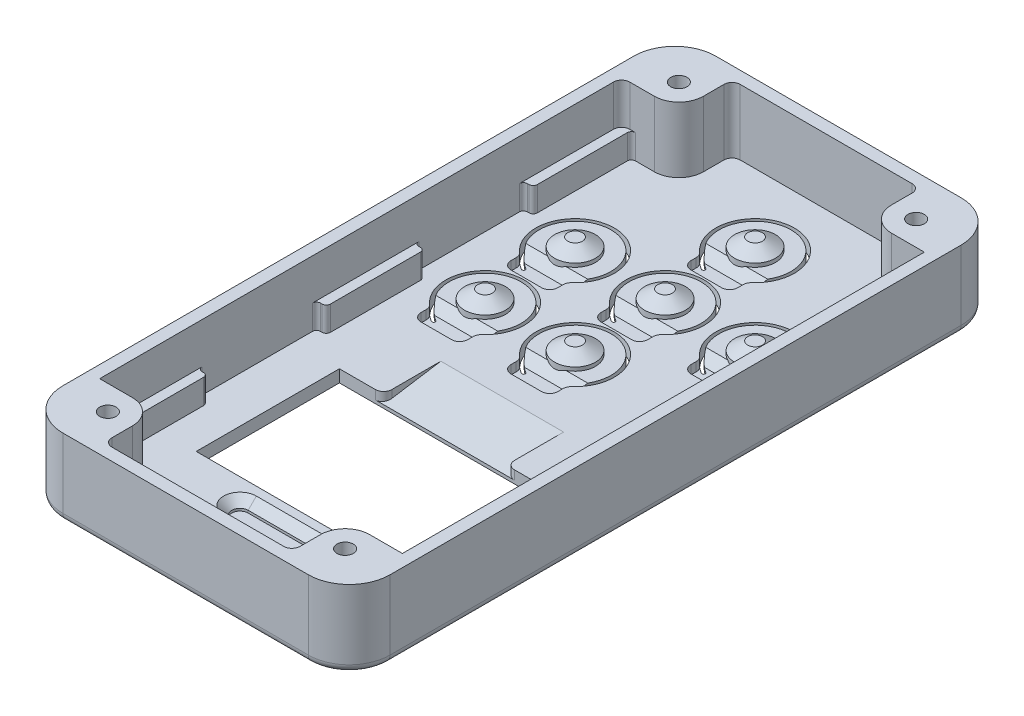
SolidWorks part; units mm, degrees
ref_plane "Front Plane" through (0, 0, 0) normal (0, 0, 1) x (1, 0, 0)
ref_plane "Top Plane" through (0, 0, 0) normal (0, 1, 0) x (1, 0, 0)
ref_plane "Right Plane" through (0, 0, 0) normal (1, 0, 0) x (0, 0, -1)
sketch "Base Sketch" plane through (0, 0, 0) normal (0, 1, 0) x (1, 0, 0)
  line L0 (0, 0) -> (40, 0)
  line L1 (40, 0) -> (40, 79.79)
  line L2 (40, 79.79) -> (0, 79.79)
  line L3 (0, 79.79) -> (0, 0)
extrude "Base" add sketch "Base Sketch" along normal blind 9.5
fillet "Corner Rounds R5" radius 5 4 edges at (0, 4.75, -79.79) (40, 4.75, -79.79) (40, 4.75, 0) (0, 4.75, 0)
shell "Shell 1.5" thickness 1.5 removed face at (20, 9.5, -39.895)
sketch "Boss Sketch" plane through (0, 0, 0) normal (0, 1, 0) x (1, 0, 0)
  line L0 (1.5, 1.5) -> (8.5, 1.5)
  line L1 (8.5, 1.5) -> (8.5, 5)
  line L2 (5.5, 8) -> (1.5, 8)
  line L3 (1.5, 8) -> (1.5, 1.5)
  line L4 (38.5, 1.5) -> (31.5, 1.5)
  line L5 (31.5, 1.5) -> (31.5, 5)
  line L6 (34.5, 8) -> (38.5, 8)
  line L7 (38.5, 8) -> (38.5, 1.5)
  line L16 (1.5, 78.29) -> (8.5, 78.29)
  line L17 (8.5, 78.29) -> (8.5, 74.79)
  line L18 (5.5, 71.79) -> (1.5, 71.79)
  line L19 (1.5, 71.79) -> (1.5, 78.29)
  line L20 (38.5, 78.29) -> (31.5, 78.29)
  line L21 (31.5, 78.29) -> (31.5, 74.79)
  line L22 (34.5, 71.79) -> (38.5, 71.79)
  line L23 (38.5, 71.79) -> (38.5, 78.29)
  arc A0 (8.5, 5) -> (5.5, 8) centre (5.4999, 4.9999) ccw
  circle A1 centre (5.5, 5) radius 1
  arc A2 (31.5, 5) -> (34.5, 8) centre (34.5001, 4.9999) cw
  circle A3 centre (34.5, 5) radius 1
  circle A5 centre (5.5, 74.79) radius 1
  circle A7 centre (34.5, 74.79) radius 1
  arc A8 (8.5, 74.79) -> (5.5, 71.79) centre (5.4999, 74.7901) cw
  arc A9 (31.5, 74.79) -> (34.5, 71.79) centre (34.5001, 74.7901) ccw
extrude "Corner Bosses + M2 Pilot Holes" add sketch "Boss Sketch" along normal blind 9.5
sketch "Ledge Sketch" plane through (0, 0, 0) normal (0, 1, 0) x (1, 0, 0)
  line L0 (1.5, 8) -> (2.7, 8)
  line L1 (2.7, 8) -> (2.7, 20)
  line L2 (2.7, 20) -> (1.5, 20)
  line L3 (1.5, 20) -> (1.5, 8)
  line L4 (37.3, 8) -> (38.5, 8)
  line L5 (38.5, 8) -> (38.5, 20)
  line L6 (38.5, 20) -> (37.3, 20)
  line L7 (37.3, 20) -> (37.3, 8)
  line L8 (1.5, 34.5) -> (2.7, 34.5)
  line L9 (2.7, 34.5) -> (2.7, 46.5)
  line L10 (2.7, 46.5) -> (1.5, 46.5)
  line L11 (1.5, 46.5) -> (1.5, 34.5)
  line L12 (37.3, 34.5) -> (38.5, 34.5)
  line L13 (38.5, 34.5) -> (38.5, 46.5)
  line L14 (38.5, 46.5) -> (37.3, 46.5)
  line L15 (37.3, 46.5) -> (37.3, 34.5)
  line L16 (1.5, 59.79) -> (2.7, 59.79)
  line L17 (2.7, 59.79) -> (2.7, 71.79)
  line L18 (2.7, 71.79) -> (1.5, 71.79)
  line L19 (1.5, 71.79) -> (1.5, 59.79)
  line L20 (37.3, 59.79) -> (38.5, 59.79)
  line L21 (38.5, 59.79) -> (38.5, 71.79)
  line L22 (38.5, 71.79) -> (37.3, 71.79)
  line L23 (37.3, 71.79) -> (37.3, 59.79)
extrude "Side Ledges" add sketch "Ledge Sketch" along normal blind 4.5
fillet "Outer Face Round R1" radius 1 8 edges at (1.4645, 0, -1.4645) (20, 0, 0) (38.5355, 0, -1.4645) (40, 0, -39.895) (38.5355, 0, -78.3255) (20, 0, -79.79) (1.4645, 0, -78.3255) (0, 0, -39.895)
sketch "Window Sketch" plane through (0, 0, 0) normal (0, 1, 0) x (1, 0, 0)
  line L0 (7.1, 14.5) -> (32.9, 14.5)
  line L1 (32.9, 14.5) -> (32.9, 31.7)
  line L2 (32.9, 31.7) -> (7.1, 31.7)
  line L3 (7.1, 31.7) -> (7.1, 14.5)
extrude "Display Window" cut sketch "Window Sketch" along normal through all
ref_plane "Mid Plane X20" through (20, 0, 0) normal (1, 0, 0) x (0, 0, -1)
sketch "Ramp Sketch" plane through (20, 0, 0) normal (1, 0, 0) x (0, 0, -1)
  line L0 (31, 0.4) -> (31.7, 0.4)
  line L1 (31.7, 0.4) -> (38.7, 1.5)
  line L2 (38.7, 1.5) -> (38.7, 2.5)
  line L3 (38.7, 2.5) -> (31, 2.5)
  line L4 (31, 2.5) -> (31, 0.4)
extrude "Cable Ramp" cut sketch "Ramp Sketch" against normal blind 7.5 and the other way blind 7.5
ref_plane "Plate Inner Face" through (0, 1.5, 0) normal (0, 1, 0) x (1, 0, 0)
sketch "LED Window Sketch" plane through (0, 1.5, 0) normal (0, 1, 0) x (1, 0, 0)
  circle A0 centre (20, 7.28) radius 1.7
  point P2 (0, 0)
  point P3 (0, 0)
  dimension "D1" = 3.4
extrude "LED Window" cut sketch "LED Window Sketch" against normal blind 1.3
sketch "Plunger Stems Sketch" plane through (0, 1.5, 0) normal (0, 1, 0) x (1, 0, 0)
  circle A0 centre (9, 47.6) radius 2.5
  circle A1 centre (20, 47.6) radius 2.5
  circle A2 centre (9, 58.6) radius 2.5
  circle A3 centre (20, 58.6) radius 2.5
  circle A4 centre (31, 58.6) radius 2.5
  circle A5 centre (20, 69.6) radius 2.5
extrude "Plunger Stems 5.0" add sketch "Plunger Stems Sketch" along normal blind 0.45
ref_plane "Plunger Cone Base" through (0, 1.95, 0) normal (0, 1, 0) x (1, 0, 0)
sketch "Plunger Cone Sketch" plane through (0, 1.95, 0) normal (0, 1, 0) x (1, 0, 0)
  circle A0 centre (9, 47.6) radius 2.5
  circle A1 centre (20, 47.6) radius 2.5
  circle A2 centre (9, 58.6) radius 2.5
  circle A3 centre (20, 58.6) radius 2.5
  circle A4 centre (31, 58.6) radius 2.5
  circle A5 centre (20, 69.6) radius 2.5
extrude "Plunger Cones to 1.8" add sketch "Plunger Cone Sketch" along normal blind 1 draft 57.995
fillet "Boss Junction Fillets R1" radius 1 8 edges at (1.5, 7, -71.79) (37.3, 3, -71.79) (37.3, 3, -8) (2.7, 3, -8) (31.5, 5.5, -78.29) (8.5, 5.5, -78.29) (31.5, 5.5, -1.5) (8.5, 5.5, -1.5)
sketch "C-Slot Sketch" plane through (0, 0, 0) normal (0, 1, 0) x (1, 0, 0)
  arc A0 (10.4434, 43.0222) -> (7.5566, 43.0222) centre (9, 47.6) ccw
  arc A1 (7.5566, 43.0222) -> (7.6769, 43.4036) centre (7.6168, 43.2129) ccw
  arc A2 (7.6769, 43.4036) -> (10.3231, 43.4036) centre (9, 47.6) cw
  arc A3 (10.3231, 43.4036) -> (10.4434, 43.0222) centre (10.3832, 43.2129) ccw
  arc A4 (21.4434, 43.0222) -> (18.5566, 43.0222) centre (20, 47.6) ccw
  arc A5 (18.5566, 43.0222) -> (18.6769, 43.4036) centre (18.6168, 43.2129) ccw
  arc A6 (18.6769, 43.4036) -> (21.3231, 43.4036) centre (20, 47.6) cw
  arc A7 (21.3231, 43.4036) -> (21.4434, 43.0222) centre (21.3832, 43.2129) ccw
  arc A8 (10.4434, 54.0222) -> (7.5566, 54.0222) centre (9, 58.6) ccw
  arc A9 (7.5566, 54.0222) -> (7.6769, 54.4036) centre (7.6168, 54.2129) ccw
  arc A10 (7.6769, 54.4036) -> (10.3231, 54.4036) centre (9, 58.6) cw
  arc A11 (10.3231, 54.4036) -> (10.4434, 54.0222) centre (10.3832, 54.2129) ccw
  arc A12 (21.4434, 54.0222) -> (18.5566, 54.0222) centre (20, 58.6) ccw
  arc A13 (18.5566, 54.0222) -> (18.6769, 54.4036) centre (18.6168, 54.2129) ccw
  arc A14 (18.6769, 54.4036) -> (21.3231, 54.4036) centre (20, 58.6) cw
  arc A15 (21.3231, 54.4036) -> (21.4434, 54.0222) centre (21.3832, 54.2129) ccw
  arc A16 (32.4434, 54.0222) -> (29.5566, 54.0222) centre (31, 58.6) ccw
  arc A17 (29.5566, 54.0222) -> (29.6769, 54.4036) centre (29.6168, 54.2129) ccw
  arc A18 (29.6769, 54.4036) -> (32.3231, 54.4036) centre (31, 58.6) cw
  arc A19 (32.3231, 54.4036) -> (32.4434, 54.0222) centre (32.3832, 54.2129) ccw
  arc A20 (21.4434, 65.0222) -> (18.5566, 65.0222) centre (20, 69.6) ccw
  arc A21 (18.5566, 65.0222) -> (18.6769, 65.4036) centre (18.6168, 65.2129) ccw
  arc A22 (18.6769, 65.4036) -> (21.3231, 65.4036) centre (20, 69.6) cw
  arc A23 (21.3231, 65.4036) -> (21.4434, 65.0222) centre (21.3832, 65.2129) ccw
sketch "Sketch10" plane through (0, 1.5, 0) normal (0, 1, 0) x (1, 0, 0)
  line L0 (11.864, 44.259) -> (11.864, 41.636)
  line L1 (11.864, 41.636) -> (6.136, 41.636)
  line L2 (6.136, 41.636) -> (6.136, 44.259)
  line L3 (6.136, 44.259) -> (11.864, 44.259)
  line L4 (22.864, 44.259) -> (22.864, 41.636)
  line L5 (22.864, 41.636) -> (17.136, 41.636)
  line L6 (17.136, 41.636) -> (17.136, 44.259)
  line L7 (17.136, 44.259) -> (22.864, 44.259)
  line L8 (11.864, 55.259) -> (11.864, 52.636)
  line L9 (11.864, 52.636) -> (6.136, 52.636)
  line L10 (6.136, 52.636) -> (6.136, 55.259)
  line L11 (6.136, 55.259) -> (11.864, 55.259)
  line L12 (22.864, 55.259) -> (22.864, 52.636)
  line L13 (22.864, 52.636) -> (17.136, 52.636)
  line L14 (17.136, 52.636) -> (17.136, 55.259)
  line L15 (17.136, 55.259) -> (22.864, 55.259)
  line L16 (33.864, 55.259) -> (33.864, 52.636)
  line L17 (33.864, 52.636) -> (28.136, 52.636)
  line L18 (28.136, 52.636) -> (28.136, 55.259)
  line L19 (28.136, 55.259) -> (33.864, 55.259)
  line L20 (22.864, 66.259) -> (22.864, 63.636)
  line L21 (22.864, 63.636) -> (17.136, 63.636)
  line L22 (17.136, 63.636) -> (17.136, 66.259)
  line L23 (17.136, 66.259) -> (22.864, 66.259)
extrude "Cut-Extrude7" cut sketch "Sketch10" against normal blind 1.1
sketch "Sketch11" plane through (0, 0, 0) normal (0, 1, 0) x (1, 0, 0)
  arc A0 (11.4, 43.4431) -> (6.6, 43.4431) centre (9, 47.6) ccw
  arc A1 (6.6, 43.4431) -> (6.8, 43.7895) centre (6.7, 43.6163) ccw
  arc A2 (6.8, 43.7895) -> (11.2, 43.7895) centre (9, 47.6) cw
  arc A3 (11.2, 43.7895) -> (11.4, 43.4431) centre (11.3, 43.6163) ccw
  arc A4 (22.4, 43.4431) -> (17.6, 43.4431) centre (20, 47.6) ccw
  arc A5 (17.6, 43.4431) -> (17.8, 43.7895) centre (17.7, 43.6163) ccw
  arc A6 (17.8, 43.7895) -> (22.2, 43.7895) centre (20, 47.6) cw
  arc A7 (22.2, 43.7895) -> (22.4, 43.4431) centre (22.3, 43.6163) ccw
  arc A8 (11.4, 54.4431) -> (6.6, 54.4431) centre (9, 58.6) ccw
  arc A9 (6.6, 54.4431) -> (6.8, 54.7895) centre (6.7, 54.6163) ccw
  arc A10 (6.8, 54.7895) -> (11.2, 54.7895) centre (9, 58.6) cw
  arc A11 (11.2, 54.7895) -> (11.4, 54.4431) centre (11.3, 54.6163) ccw
  arc A12 (22.4, 54.4431) -> (17.6, 54.4431) centre (20, 58.6) ccw
  arc A13 (17.6, 54.4431) -> (17.8, 54.7895) centre (17.7, 54.6163) ccw
  arc A14 (17.8, 54.7895) -> (22.2, 54.7895) centre (20, 58.6) cw
  arc A15 (22.2, 54.7895) -> (22.4, 54.4431) centre (22.3, 54.6163) ccw
  arc A16 (33.4, 54.4431) -> (28.6, 54.4431) centre (31, 58.6) ccw
  arc A17 (28.6, 54.4431) -> (28.8, 54.7895) centre (28.7, 54.6163) ccw
  arc A18 (28.8, 54.7895) -> (33.2, 54.7895) centre (31, 58.6) cw
  arc A19 (33.2, 54.7895) -> (33.4, 54.4431) centre (33.3, 54.6163) ccw
  arc A20 (22.4, 65.4431) -> (17.6, 65.4431) centre (20, 69.6) ccw
  arc A21 (17.6, 65.4431) -> (17.8, 65.7895) centre (17.7, 65.6163) ccw
  arc A22 (17.8, 65.7895) -> (22.2, 65.7895) centre (20, 69.6) cw
  arc A23 (22.2, 65.7895) -> (22.4, 65.4431) centre (22.3, 65.6163) ccw
extrude "Button C-Slots 300deg 0.4" cut sketch "Sketch11" along normal through all
chamfer "Chamfer1" distance 1.1 angle 45 6 edges at (9, 1.5, -44.259) (20, 1.5, -66.259) (31, 1.5, -55.259) (20, 1.5, -55.259) (9, 1.5, -55.259) (20, 1.5, -44.259)
fillet "Fillet1" radius 1 24 edges at (11.864, 0.95, -43.7481) (11.864, 0.95, -41.636) (6.136, 0.95, -41.636) (6.136, 0.95, -43.7481) (22.864, 0.95, -63.636) (22.864, 0.95, -65.7481) (17.136, 0.95, -63.636) (17.136, 0.95, -65.7481) (33.864, 0.95, -52.636) (33.864, 0.95, -54.7481) (28.136, 0.95, -52.636) (28.136, 0.95, -54.7481) (22.864, 0.95, -52.636) (22.864, 0.95, -54.7481) (17.136, 0.95, -52.636) (17.136, 0.95, -54.7481) (11.864, 0.95, -52.636) (11.864, 0.95, -54.7481) (6.136, 0.95, -52.636) (6.136, 0.95, -54.7481) (22.864, 0.95, -41.636) (22.864, 0.95, -43.7481) (17.136, 0.95, -41.636) (17.136, 0.95, -43.7481)
fillet "Fillet2" radius 0.5 17 edges at (2.7, 3, -71.79) (1.5, 3, -59.79) (2.7, 3, -59.79) (38.5, 3, -59.79) (37.3, 3, -59.79) (38.5, 3, -46.5) (37.3, 3, -46.5) (2.7, 3, -46.5) (1.5, 3, -46.5) (38.5, 3, -34.5) (37.3, 3, -34.5) (2.7, 3, -34.5) (1.5, 3, -34.5) (38.5, 3, -20) (37.3, 3, -20) (2.7, 3, -20) (1.5, 3, -20)
fillet "Fillet3" radius 1 2 edges at (27.5, 0.95, -31.7) (12.5, 0.95, -31.7)
sketch "Button Symbols Cut Sketch" plane through (0, 0, 0) normal (0, 1, 0) x (1, 0, 0)
  line L0 (7.0908, 45.6908) -> (7.7272, 46.3272)
  line L1 (10.2728, 46.3272) -> (10.9092, 45.6908)
  line L2 (8.55, 47.2) -> (9.45, 47.2)
  line L3 (9.45, 47.2) -> (9.45, 44.4)
  line L4 (9.45, 44.4) -> (8.55, 44.4)
  line L5 (8.55, 44.4) -> (8.55, 47.2)
  line L6 (20, 44.8) -> (22.4249, 49)
  line L7 (22.4249, 49) -> (17.5751, 49)
  line L8 (17.5751, 49) -> (20, 44.8)
  line L9 (6.2, 58.6) -> (10.4, 56.1751)
  line L10 (10.4, 56.1751) -> (10.4, 61.0249)
  line L11 (10.4, 61.0249) -> (6.2, 58.6)
  line L12 (33.8, 58.6) -> (29.6, 61.0249)
  line L13 (29.6, 61.0249) -> (29.6, 56.1751)
  line L14 (29.6, 56.1751) -> (33.8, 58.6)
  line L15 (20, 72.4) -> (17.5751, 68.2)
  line L16 (17.5751, 68.2) -> (22.4249, 68.2)
  line L17 (22.4249, 68.2) -> (20, 72.4)
  arc A0 (10.9092, 45.6908) -> (7.0908, 45.6908) centre (9, 47.6) ccw
  arc A1 (7.7272, 46.3272) -> (10.2728, 46.3272) centre (9, 47.6) cw
  circle A2 centre (20, 58.6) radius 2.4
  circle A3 centre (20, 58.6) radius 1.5
sketch "Button Symbols Inlay Sketch" plane through (0, 0, 0) normal (0, 1, 0) x (1, 0, 0)
  line L0 (7.0908, 45.6908) -> (7.7272, 46.3272)
  line L1 (10.2728, 46.3272) -> (10.9092, 45.6908)
  line L2 (8.55, 47.2) -> (9.45, 47.2)
  line L3 (9.45, 47.2) -> (9.45, 44.4)
  line L4 (9.45, 44.4) -> (8.55, 44.4)
  line L5 (8.55, 44.4) -> (8.55, 47.2)
  line L6 (20, 44.8) -> (22.4249, 49)
  line L7 (22.4249, 49) -> (17.5751, 49)
  line L8 (17.5751, 49) -> (20, 44.8)
  line L9 (6.2, 58.6) -> (10.4, 56.1751)
  line L10 (10.4, 56.1751) -> (10.4, 61.0249)
  line L11 (10.4, 61.0249) -> (6.2, 58.6)
  line L12 (33.8, 58.6) -> (29.6, 61.0249)
  line L13 (29.6, 61.0249) -> (29.6, 56.1751)
  line L14 (29.6, 56.1751) -> (33.8, 58.6)
  line L15 (20, 72.4) -> (17.5751, 68.2)
  line L16 (17.5751, 68.2) -> (22.4249, 68.2)
  line L17 (22.4249, 68.2) -> (20, 72.4)
  arc A0 (10.9092, 45.6908) -> (7.0908, 45.6908) centre (9, 47.6) ccw
  arc A1 (7.7272, 46.3272) -> (10.2728, 46.3272) centre (9, 47.6) cw
  circle A2 centre (20, 58.6) radius 2.4
  circle A3 centre (20, 58.6) radius 1.5
sketch "Sketch14" plane through (0, 0, 0) normal (0, 1, 0) x (1, 0, 0)
  line L0 (8.4, 47) -> (8.4, 45.2)
  line L1 (9.6, 45.2) -> (9.6, 47)
  line L2 (20.5196, 44.9) -> (22.7713, 48.8)
  line L3 (22.2517, 49.7) -> (17.7483, 49.7)
  line L4 (17.2287, 48.8) -> (19.4804, 44.9)
  line L5 (6.1, 58.0804) -> (10, 55.8287)
  line L6 (10.9, 56.3483) -> (10.9, 60.8517)
  line L7 (10, 61.3713) -> (6.1, 59.1196)
  line L8 (33.9, 59.1196) -> (30, 61.3713)
  line L9 (29.1, 60.8517) -> (29.1, 56.3483)
  line L10 (30, 55.8287) -> (33.9, 58.0804)
  line L11 (19.4804, 72.5) -> (17.2287, 68.6)
  line L12 (17.7483, 67.7) -> (22.2517, 67.7)
  line L13 (22.7713, 68.6) -> (20.5196, 72.5)
  arc A0 (11.4513, 45.5431) -> (6.5487, 45.5431) centre (9, 47.6) ccw
  arc A1 (6.5487, 45.5431) -> (7.4679, 46.3144) centre (7.0083, 45.9288) ccw
  arc A2 (7.4679, 46.3144) -> (10.5321, 46.3144) centre (9, 47.6) cw
  arc A3 (10.5321, 46.3144) -> (11.4513, 45.5431) centre (10.9917, 45.9288) ccw
  arc A4 (8.4, 45.2) -> (9.6, 45.2) centre (9, 45.2) ccw
  arc A5 (9.6, 47) -> (8.4, 47) centre (9, 47) ccw
  arc A6 (19.4804, 44.9) -> (20.5196, 44.9) centre (20, 45.2) ccw
  arc A7 (22.7713, 48.8) -> (22.2517, 49.7) centre (22.2517, 49.1) ccw
  arc A8 (17.7483, 49.7) -> (17.2287, 48.8) centre (17.7483, 49.1) ccw
  arc A9 (6.1, 59.1196) -> (6.1, 58.0804) centre (6.4, 58.6) ccw
  arc A10 (10, 55.8287) -> (10.9, 56.3483) centre (10.3, 56.3483) ccw
  arc A11 (10.9, 60.8517) -> (10, 61.3713) centre (10.3, 60.8517) ccw
  circle A12 centre (20, 58.6) radius 3.1
  circle A13 centre (20, 58.6) radius 1.9
  arc A14 (33.9, 58.0804) -> (33.9, 59.1196) centre (33.6, 58.6) ccw
  arc A15 (30, 61.3713) -> (29.1, 60.8517) centre (29.7, 60.8517) ccw
  arc A16 (29.1, 56.3483) -> (30, 55.8287) centre (29.7, 56.3483) ccw
  arc A17 (20.5196, 72.5) -> (19.4804, 72.5) centre (20, 72.2) ccw
  arc A18 (17.2287, 68.6) -> (17.7483, 67.7) centre (17.7483, 68.3) ccw
  arc A19 (22.2517, 67.7) -> (22.7713, 68.6) centre (22.2517, 68.3) ccw
extrude "Button Symbol Recess 0.4" cut sketch "Sketch14" along normal blind 0.4
sketch "Sketch15" plane through (0, 0, 0) normal (0, 1, 0) x (1, 0, 0)
  line L0 (8.4, 47) -> (8.4, 45.2)
  line L1 (9.6, 45.2) -> (9.6, 47)
  line L2 (20.5196, 44.9) -> (22.7713, 48.8)
  line L3 (22.2517, 49.7) -> (17.7483, 49.7)
  line L4 (17.2287, 48.8) -> (19.4804, 44.9)
  line L5 (6.1, 58.0804) -> (10, 55.8287)
  line L6 (10.9, 56.3483) -> (10.9, 60.8517)
  line L7 (10, 61.3713) -> (6.1, 59.1196)
  line L8 (33.9, 59.1196) -> (30, 61.3713)
  line L9 (29.1, 60.8517) -> (29.1, 56.3483)
  line L10 (30, 55.8287) -> (33.9, 58.0804)
  line L11 (19.4804, 72.5) -> (17.2287, 68.6)
  line L12 (17.7483, 67.7) -> (22.2517, 67.7)
  line L13 (22.7713, 68.6) -> (20.5196, 72.5)
  arc A0 (11.4513, 45.5431) -> (6.5487, 45.5431) centre (9, 47.6) ccw
  arc A1 (6.5487, 45.5431) -> (7.4679, 46.3144) centre (7.0083, 45.9288) ccw
  arc A2 (7.4679, 46.3144) -> (10.5321, 46.3144) centre (9, 47.6) cw
  arc A3 (10.5321, 46.3144) -> (11.4513, 45.5431) centre (10.9917, 45.9288) ccw
  arc A4 (8.4, 45.2) -> (9.6, 45.2) centre (9, 45.2) ccw
  arc A5 (9.6, 47) -> (8.4, 47) centre (9, 47) ccw
  arc A6 (19.4804, 44.9) -> (20.5196, 44.9) centre (20, 45.2) ccw
  arc A7 (22.7713, 48.8) -> (22.2517, 49.7) centre (22.2517, 49.1) ccw
  arc A8 (17.7483, 49.7) -> (17.2287, 48.8) centre (17.7483, 49.1) ccw
  arc A9 (6.1, 59.1196) -> (6.1, 58.0804) centre (6.4, 58.6) ccw
  arc A10 (10, 55.8287) -> (10.9, 56.3483) centre (10.3, 56.3483) ccw
  arc A11 (10.9, 60.8517) -> (10, 61.3713) centre (10.3, 60.8517) ccw
  circle A12 centre (20, 58.6) radius 3.1
  circle A13 centre (20, 58.6) radius 1.9
  arc A14 (33.9, 58.0804) -> (33.9, 59.1196) centre (33.6, 58.6) ccw
  arc A15 (30, 61.3713) -> (29.1, 60.8517) centre (29.7, 60.8517) ccw
  arc A16 (29.1, 56.3483) -> (30, 55.8287) centre (29.7, 56.3483) ccw
  arc A17 (20.5196, 72.5) -> (19.4804, 72.5) centre (20, 72.2) ccw
  arc A18 (17.2287, 68.6) -> (17.7483, 67.7) centre (17.7483, 68.3) ccw
  arc A19 (22.2517, 67.7) -> (22.7713, 68.6) centre (22.2517, 68.3) ccw
extrude "Button Symbol Inlays 0.4 (colour 2)" add sketch "Sketch15" along normal blind 0.4 separate body
sketch "I2C Header Pocket Sketch" plane through (0, 1.5, 0) normal (0, 1, 0) x (1, 0, 0)
  line L0 (15.5, 9.4) -> (24.5, 9.4)
  line L1 (25.5, 10.4) -> (25.5, 11.9)
  line L2 (24.5, 12.9) -> (15.5, 12.9)
  line L3 (14.5, 11.9) -> (14.5, 10.4)
  line L4 (32.9, 14.5) -> (7.1, 14.5) construction
  arc A0 (24.5, 9.4) -> (25.5, 10.4) centre (24.5, 10.4) ccw
  arc A1 (25.5, 11.9) -> (24.5, 12.9) centre (24.5, 11.9) ccw
  arc A2 (15.5, 12.9) -> (14.5, 11.9) centre (15.5, 11.9) ccw
  arc A3 (14.5, 10.4) -> (15.5, 9.4) centre (15.5, 10.4) ccw
  point P12 (0, 0)
  point P15 (0, 0)
  point P16 (0, 0)
  dimension "D3" = 1
  dimension "D1" = 1.6
  dimension "D2" = 11
  dimension "D4" = 2.6
sketch "Sketch17" plane through (0, 1.5, 0) normal (0, 1, 0) x (1, 0, 0)
  line L0 (15.2, 10.45) -> (24.8, 10.45)
  line L1 (24.8, 11.85) -> (15.2, 11.85)
  arc A0 (24.8, 10.45) -> (24.8, 11.85) centre (24.8, 11.15) ccw
  arc A1 (15.2, 11.85) -> (15.2, 10.45) centre (15.2, 11.15) ccw
sketch "Sketch18" plane through (0, 0, -14.5) normal (0, 0, -1) x (-1, 0, 0)
  line L4 (-32.9, 1.5) -> (-32.9, 0)
  line L5 (-32.9, 0) -> (-7.1, 0)
  line L6 (-7.1, 0) -> (-7.1, 1.5)
  line L7 (-7.1, 1.5) -> (-32.9, 1.5)
  line L8 (-32.9, 1.5) -> (-32.9, 0)
  line L9 (-32.9, 0) -> (-7.1, 0)
  line L10 (-7.1, 0) -> (-7.1, 1.5)
  line L11 (-7.1, 1.5) -> (-32.9, 1.5)
  dimension "D1" = 0
extrude "Cut-Extrude16" cut sketch "Sketch18" against normal blind 0.3
sketch "Sketch19" plane through (0, 1.5, 0) normal (0, 1, 0) x (1, 0, 0)
  line L0 (15.2999, 10.35) -> (24.7001, 10.35)
  line L1 (25.5, 11.1499) -> (25.5, 11.1501)
  line L2 (24.7001, 11.95) -> (15.2999, 11.95)
  line L3 (14.5, 11.1501) -> (14.5, 11.1499)
  arc A0 (24.7001, 10.35) -> (25.5, 11.1499) centre (24.7001, 11.1499) ccw
  arc A1 (25.5, 11.1501) -> (24.7001, 11.95) centre (24.7001, 11.1501) ccw
  arc A2 (15.2999, 11.95) -> (14.5, 11.1501) centre (15.2999, 11.1501) ccw
  arc A3 (14.5, 11.1499) -> (15.2999, 10.35) centre (15.2999, 11.1499) ccw
sketch "Sketch20" plane through (0, 1.5, 0) normal (0, 1, 0) x (1, 0, 0)
  line L0 (15.5, 10.15) -> (24.5, 10.15)
  line L1 (24.5, 12.15) -> (15.5, 12.15)
  arc A0 (24.5, 10.15) -> (24.5, 12.15) centre (24.5, 11.15) ccw
  arc A1 (15.5, 12.15) -> (15.5, 10.15) centre (15.5, 11.15) ccw
extrude "I2C Header Lead Pocket 2.0 (0.2 skin)" cut sketch "Sketch20" against normal blind 1.3
chamfer "Chamfer3" distance 1 angle 45 4 edges at (20, 1.5, -12.15) (14.5, 1.5, -11.15) (25.5, 1.5, -11.15) (20, 1.5, -10.15)
